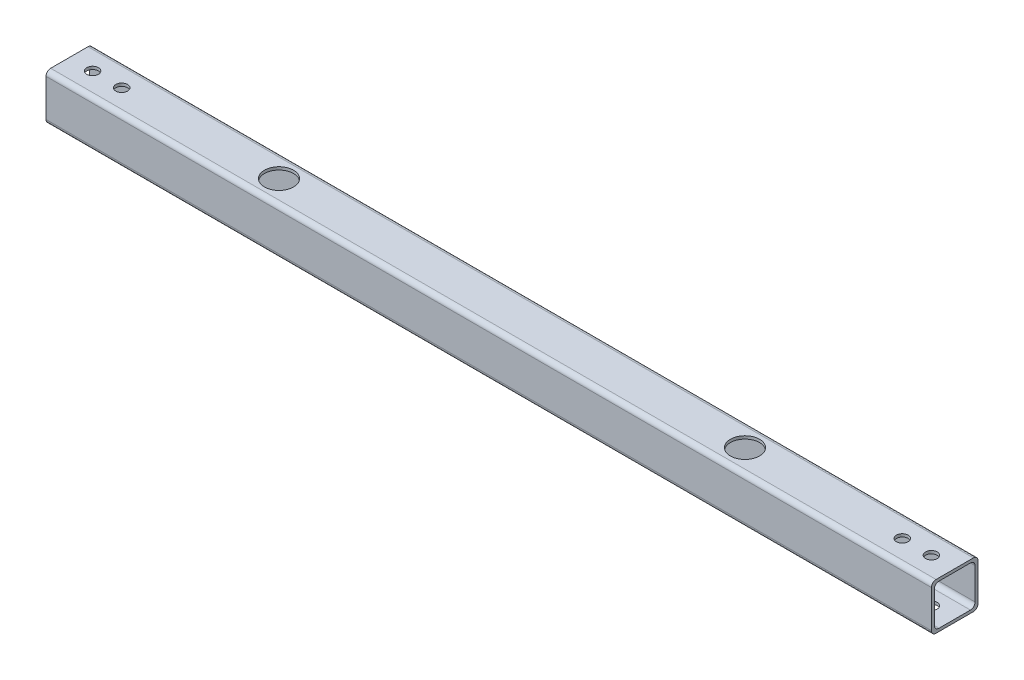
SolidWorks part; units mm, degrees
material "ASTM A36 Steel"
ref_plane "Front Plane" through (0, 0, 0) normal (0, 0, 1) x (1, 0, 0)
ref_plane "Top Plane" through (0, 0, 0) normal (0, 1, 0) x (1, 0, 0)
ref_plane "Right Plane" through (0, 0, 0) normal (1, 0, 0) x (0, 0, -1)
sketch "Sketch1" plane through (0, 0, 0) normal (1, 0, 0) x (0, 0, -1)
  line L1 (-12.7, -12.7) -> (12.7, -12.7)
  line L2 (-12.7, -12.7) -> (-12.7, 12.7)
  line L3 (-12.7, 12.7) -> (12.7, 12.7)
  line L4 (12.7, -12.7) -> (12.7, 12.7)
  line L5 (-12.7, -12.7) -> (12.7, 12.7) construction
  line L6 (-12.7, 12.7) -> (12.7, -12.7) construction
  line L7 (-11.1125, -11.1125) -> (11.1125, -11.1125)
  line L8 (-11.1125, -11.1125) -> (-11.1125, 11.1125)
  line L9 (-11.1125, 11.1125) -> (11.1125, 11.1125)
  line L10 (11.1125, -11.1125) -> (11.1125, 11.1125)
  line L11 (-11.1125, -11.1125) -> (11.1125, 11.1125) construction
  line L12 (-11.1125, 11.1125) -> (11.1125, -11.1125) construction
  point P0 (0, 0)
  point P3 (0, 0)
  dimension "D1" = 25.4
  dimension "D2" = 1.5875
  dimension "D3" = 25.4
extrude "Boss-Extrude1" add sketch "Sketch1" along normal mid plane 482.6
fillet "Fillet1" radius 2.54 8 edges at (0, -11.1125, 11.1125) (0, -11.1125, -11.1125) (0, 11.1125, -11.1125) (0, 11.1125, 11.1125) (0, -12.7, 12.7) (0, -12.7, -12.7) (0, 12.7, -12.7) (0, 12.7, 12.7)
sketch "Sketch2" plane through (0, -12.7, 0) normal (0, 1, 0) x (1, 0, 0)
  circle A0 centre (127, 0) radius 3.175
  circle A1 centre (-127, 0) radius 3.175
  dimension "D1" = 6.35
  dimension "D2" = 6.35
  dimension "D3" = 127
  dimension "D4" = 127
extrude "Cut-Extrude1" cut sketch "Sketch2" along normal up to next
sketch "Sketch3" plane through (0, 12.7, 0) normal (0, 1, 0) x (1, 0, 0)
  circle A0 centre (-127, 0) radius 7.9375
  circle A1 centre (127, 0) radius 7.9375
  dimension "D1" = 15.875
  dimension "D2" = 15.875
  dimension "D3" = 127
  dimension "D4" = 127
extrude "Cut-Extrude2" cut sketch "Sketch3" against normal up to next
sketch "Sketch4" plane through (0, 12.7, 0) normal (0, 1, 0) x (1, 0, 0)
  line L0 (-241.3, 0) -> (241.3, 0) construction
  line L1 (-241.3, 10.16) -> (-241.3, -10.16) construction
  line L2 (241.3, 10.16) -> (241.3, -10.16) construction
  circle A0 centre (-228.6, 0) radius 3.175
  circle A1 centre (-212.725, 0) radius 3.175
  dimension "D1" = 6.35
  dimension "D2" = 12.7
  dimension "D3" = 28.575
extrude "Cut-Extrude3" cut sketch "Sketch4" against normal up to surface (25.4 mm away) up to face at (-127, -12.7, 3.175)
mirror "Mirror1" about plane through (0, 0, 0) normal (1, 0, 0) of "Cut-Extrude3"
